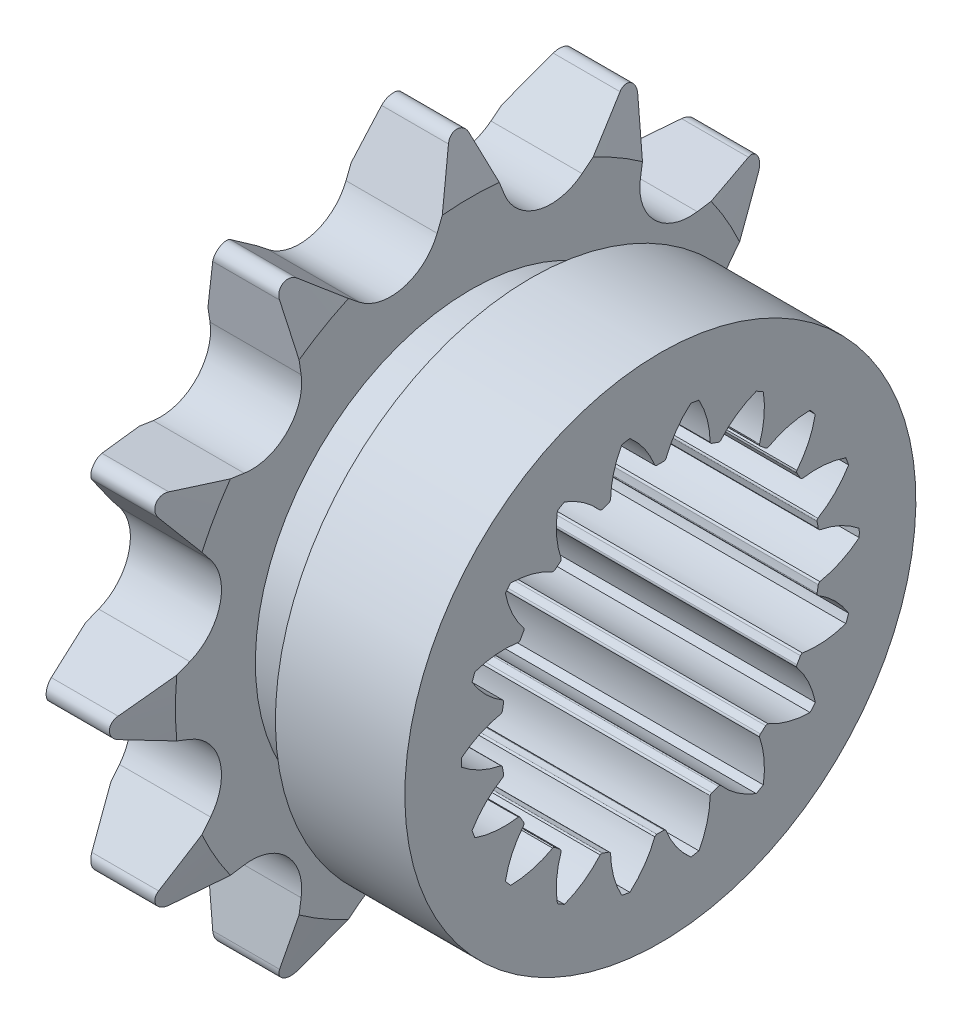
SolidWorks part; units mm, degrees
material "1144"
ref_plane "Front Plane" through (0, 0, 0) normal (0, 0, 1) x (1, 0, 0)
ref_plane "Top Plane" through (0, 0, 0) normal (0, 1, 0) x (1, 0, 0)
ref_plane "Right Plane" through (0, 0, 0) normal (1, 0, 0) x (0, 0, -1)
ref_axis "Axis1" through (-63.0158, 0, 0) along (1, 0, 0)
sketch "Sketch1" plane through (0, 0, 0) normal (0, 0, 1) x (1, 0, 0)
  line L0 (3.6068, 17.0561) -> (3.6068, 0) construction
  line L1 (22.225, 0) -> (22.225, 20.2311)
  line L3 (7.2136, 17.0561) -> (0, 17.0561)
  line L7 (0, 27.5082) -> (0, 30.0482) construction
  line L8 (0, 27.5082) -> (7.2136, 27.5082)
  line L9 (22.225, 0) -> (0, 0)
  line L10 (0, 0) -> (-84.1773, 0) construction
  line L11 (0, 17.0561) -> (0, 27.5082) construction
  line L12 (7.2136, 27.5082) -> (73.2462, 27.5082) construction
  line L13 (22.225, 0) -> (22.225, -20.2311) construction
  line L14 (3.6068, 0) -> (3.6068, -17.0561)
  line L15 (-15.4432, -17.0561) -> (22.6568, -17.0561)
  point P11 (0, 30.0482)
  dimension "D1" = 2.54
  dimension "hub_dia" = 40.4622
  dimension "width_teetth" = 7.2136
  dimension "D2" = 38.1
  dimension "length_thru" = 22.225
  dimension "OD" = 55.0164
  dimension "length_over_teeth" = 7.2136
  dimension "recess_hub_diam" = 34.1122
  dimension "hub_type" = 22.225
  dimension "projection 1" = 15.0114
  dimension "projection 2" = 0
sketch "Sketch2" plane through (0, 0, 0) normal (1, 0, 0) x (0, 0, -1)
  line L0 (0, 0) -> (0, 27.5082) construction
  line L1 (0, 0) -> (-13.7541, 23.8228) construction
  line L2 (0, 0) -> (-6.3502, 23.6991) construction
  line L3 (-0.8057, 26.9597) -> (-2.6638, 22.246)
  line L4 (-2.6638, 22.246) -> (-6.3502, 23.6991) construction
  line L5 (-0.8217, 27.4959) -> (0, 0) construction
  line L6 (-2.735, 27.3719) -> (0, 0) construction
  line L7 (-6.3502, 23.6991) -> (-2.4074, 24.0931) construction
  arc A1 (0, 27.5082) -> (-13.7541, 23.8228) centre (0, 0) ccw
  circle A2 centre (0, 0) radius 24.5351 construction
  circle A3 centre (-6.3502, 23.6991) radius 3.9624
  arc A4 (0, 27.5082) -> (-0.8057, 26.9597) centre (0, 26.6421) ccw
  dimension "pitch_diam" = 49.0703
  dimension "roller_diam" = 7.9248
  dimension "D1" = 1.712
  dimension "ang_1" = 30
  dimension "OD/2" = 27.5082
sketch "Taper Per Foot" plane through (0, 0, 0) normal (0, 0, 1) x (1, 0, 0)
  line L0 (22.225, 0) -> (22.225, 127)
  line L1 (22.225, 0) -> (22.225, 20.2311) construction
  line L2 (22.225, 127) -> (-282.575, 6.35)
  line L3 (-282.575, 6.35) -> (-282.575, 0)
  line L4 (-282.575, 0) -> (22.225, 0)
  line L5 (-282.575, 0) -> (-285.7823, 0) construction
  line L6 (-282.575, 6.35) -> (22.225, 6.35)
  line L7 (22.225, 6.35) -> (22.225, 127)
  dimension "1 Ft" = 304.8
  dimension "1 in" = 254
  dimension "Small End Diam" = 12.7
  dimension "Large End Diam" = 12.7
ref_plane "Plane1" through (7.2136, 0, 0) normal (1, 0, 0) x (0, 0, -1)
ref_plane "Plane2" through (7.2136, 0, 0) normal (1, 0, 0) x (0, 0, -1)
ref_plane "Plane3" through (0, 17.0561, 0) normal (-1, 0, 0) x (0, 0, 1)
ref_plane "Plane4" through (22.225, 0, 0) normal (1, 0, 0) x (0, 0, -1)
ref_plane "Plane5" through (3.6068, 0, 0) normal (1, 0, 0) x (0, 0, -1)
sketch "Sketch13" plane through (0, 0, 0) normal (0, 0, 1) x (1, 0, 0)
  line L0 (22.225, 0) -> (22.225, 20.2311) construction
  line L1 (0, 0) -> (22.225, 0)
  line L2 (0, 0) -> (0, 27.5082)
  line L3 (0, 27.5082) -> (22.225, 27.5082)
  line L4 (22.225, 0) -> (22.225, 27.5082)
revolve "Revolve1" add sketch "Sketch13" angle 360 about L10
sketch "Sketch6" plane through (0, -16.51, 0) normal (1, 0, 0) x (0, 0, -1)
  line L0 (-0.8057, 43.4697) -> (-2.6638, 38.756) construction
  line L1 (-0.8057, 43.4697) -> (-2.6638, 38.756)
  line L2 (-6.3502, 40.2091) -> (0, 16.51) construction
  line L3 (-12.7821, 40.2607) -> (-8.8161, 37.1075)
  arc A0 (0, 44.0182) -> (-0.8057, 43.4697) centre (0, 43.1521) ccw construction
  arc A1 (0, 44.0182) -> (-0.8057, 43.4697) centre (0, 43.1521) ccw
  arc A2 (-13.7541, 40.3328) -> (-12.7821, 40.2607) centre (-13.3211, 39.5828) cw
  arc A3 (-2.6638, 38.756) -> (-8.8161, 37.1075) centre (-6.3502, 40.2091) cw
  arc A4 (0, 44.0182) -> (-13.7541, 40.3328) centre (0, 16.51) ccw
extrude "Cut-Extrude1" cut sketch "Sketch6" along normal up to vertex (7.2136 mm away) up to point (7.2136, 17.0561, 0)
pattern_circular "CirPattern1" count 12 over 360 about axis through (-63.0158, 0, 0) along (1, 0, 0) of "Cut-Extrude1"
sketch "Sketch15" plane through (0, 0, 0) normal (0, 0, 1) x (1, 0, 0)
  line L1 (134.2136, 20.2311) -> (7.2136, 20.2311)
  line L2 (134.2136, 20.2311) -> (134.2136, 42.7482)
  line L3 (134.2136, 42.7482) -> (7.2136, 42.7482)
  line L4 (7.2136, 20.2311) -> (7.2136, 42.7482)
  line L5 (3.6068, 216.4797) -> (3.6068, 17.0561) construction
  line L6 (-127, 20.2311) -> (0, 20.2311)
  line L7 (0, 20.2311) -> (0, 42.7482)
  line L8 (-127, 42.7482) -> (0, 42.7482)
  line L9 (-127, 20.2311) -> (-127, 42.7482)
  dimension "D1" = 12.7
  dimension "D2" = 127
revolve "hub Cut-Revolve3" cut sketch "Sketch15" angle 360 about L10
sketch "Sketch4" plane through (0, 0, 0) normal (0, 0, 1) x (1, 0, 0)
  line L0 (0, 27.5082) -> (1.1045, 27.5082)
  line L2 (1.1045, 27.5082) -> (0, 23.3861)
  line L4 (0, 23.3861) -> (0, 27.5082)
  line L5 (3.6068, 27.5082) -> (3.6068, 44.9612) construction
  line L6 (7.2136, 27.5082) -> (6.1091, 27.5082)
  line L7 (7.2136, 23.3861) -> (7.2136, 27.5082)
  line L8 (6.1091, 27.5082) -> (7.2136, 23.3861)
  line L9 (0, 0) -> (-52.1231, 0) construction
  line L10 (0, 0) -> (-84.1773, 0) construction
  line L17 (0, 27.5082) -> (7.2136, 27.5082) construction
  dimension "D1" = 15
  dimension "D2" = 4.1221
revolve "Teeth Chamfer" cut sketch "Sketch4" angle 360 about L9
sketch "Sketch16" plane through (0, 0, 0) normal (0, 0, 1) x (1, 0, 0)
  line L1 (7.2136, 20.2311) -> (11.9761, 20.2311)
  line L2 (7.2136, 20.2311) -> (7.2136, 17.0561)
  line L3 (7.2136, 17.0561) -> (11.9761, 17.0561)
  line L4 (11.9761, 20.2311) -> (11.9761, 17.0561)
  line L5 (11.9761, 20.2311) -> (22.225, 20.2311) construction
  dimension "recess_width" = 4.7625
  dimension "recess_height" = 3.175
revolve "Recess" cut sketch "Sketch16" angle 360 about L10
sketch "Sketch32" plane through (22.225, 0, 0) normal (1, 0, 0) x (0, 0, -1)
  circle A1 centre (0, 0) radius 20.2311
  circle A2 centre (0, 0) radius 20.2311
  dimension "D1" = 0
extrude "Collar Reduction" [suppressed] cut sketch "Sketch32" against normal offset from surface (2.455 mm away) 19.77
ref_plane "Sprocket Teeth Center" through (3.6068, 0, 0) normal (-1, 0, 0) x (0, 0, 1)
sketch "Sketch35" plane through (3.6068, 0, 0) normal (1, 0, 0) x (0, 0, -1)
  circle A0 centre (0, 0) radius 24.5351 construction
  circle A1 centre (0, 0) radius 24.5351 construction
sketch "Sketch36" plane through (0, 0, 0) normal (-1, 0, 0) x (0, 0, 1)
  arc A34 (-7.5926, 13.7968) -> (-4.773, 11.8201) centre (-10.1337, 7.1728) cw
  arc A35 (-4.773, 11.8201) -> (-4.5847, 11.7902) centre (-4.6432, 12.0297) ccw
  arc A36 (-0.6644, 3.068) -> (-0.7894, 2.924) centre (-0.8986, 3.1451) cw
  arc A37 (-4.5847, 11.7902) -> (-4.0582, 11.9816) centre (0, 0) cw
  arc A38 (-8.1521, 13.4738) -> (-7.5639, 13.8125) centre (0, 0) cw
  arc A39 (-8.3407, 9.5111) -> (-7.9114, 9.8711) centre (0, 0) cw
  arc A40 (-7.85, 10.0436) -> (-7.9183, 9.8655) centre (-8.0965, 10.0359) cw
  arc A41 (-8.1521, 13.4738) -> (-7.85, 10.0436) centre (-1.145, 12.3625) ccw
  arc A42 (-2.4159, 15.5616) -> (-0.4424, 12.7398) centre (-7.0693, 10.2062) cw
  arc A43 (-0.4424, 12.7398) -> (-0.2757, 12.6472) centre (-0.2487, 12.8923) ccw
  arc A44 (-0.2757, 12.6472) -> (0.2845, 12.647) centre (0, 0) cw
  arc A45 (-3.0522, 15.4494) -> (-2.3836, 15.5666) centre (0, 0) cw
  arc A46 (-4.5847, 11.7902) -> (-4.0582, 11.9816) centre (0, 0) cw
  arc A47 (-3.9415, 12.1228) -> (-4.0666, 11.9788) centre (-4.1757, 12.1999) cw
  arc A48 (-3.0522, 15.4494) -> (-3.9415, 12.1228) centre (3.1523, 12.0085) ccw
  arc A49 (3.0522, 15.4494) -> (3.9415, 12.1228) centre (-3.1523, 12.0085) cw
  arc A50 (3.9415, 12.1228) -> (4.0666, 11.9788) centre (4.1757, 12.1999) ccw
  arc A51 (4.0666, 11.9788) -> (4.5929, 11.787) centre (0, 0) cw
  arc A52 (2.4159, 15.5616) -> (3.0842, 15.443) centre (0, 0) cw
  arc A53 (-0.2757, 12.6472) -> (0.2845, 12.647) centre (0, 0) cw
  arc A54 (0.4424, 12.7398) -> (0.2757, 12.6472) centre (0.2487, 12.8923) cw
  arc A55 (2.4159, 15.5616) -> (0.4424, 12.7398) centre (7.0693, 10.2062) ccw
  arc A56 (8.1521, 13.4738) -> (7.85, 10.0436) centre (1.145, 12.3625) cw
  arc A57 (7.85, 10.0436) -> (7.9183, 9.8655) centre (8.0965, 10.0359) ccw
  arc A58 (7.9183, 9.8655) -> (8.3473, 9.5053) centre (0, 0) cw
  arc A59 (7.5926, 13.7968) -> (8.18, 13.4568) centre (0, 0) cw
  arc A60 (4.0666, 11.9788) -> (4.5929, 11.787) centre (0, 0) cw
  arc A61 (4.773, 11.8201) -> (4.5847, 11.7902) centre (4.6432, 12.0297) cw
  arc A62 (7.5926, 13.7968) -> (4.773, 11.8201) centre (10.1337, 7.1728) ccw
  arc A63 (12.2688, 9.873) -> (10.8117, 6.753) centre (5.3042, 11.2253) cw
  arc A64 (10.8117, 6.753) -> (10.815, 6.5624) centre (11.0407, 6.6616) ccw
  arc A65 (10.815, 6.5624) -> (11.0949, 6.0771) centre (0, 0) cw
  arc A66 (11.8535, 10.368) -> (12.2892, 9.8476) centre (0, 0) cw
  arc A67 (7.9183, 9.8655) -> (8.3473, 9.5053) centre (0, 0) cw
  arc A68 (8.5279, 9.4748) -> (8.3407, 9.5111) centre (8.4775, 9.7162) cw
  arc A69 (11.8535, 10.368) -> (8.5279, 9.4748) centre (11.9758, 3.2743) ccw
  arc A70 (14.9057, 5.0814) -> (12.4694, 2.6479) centre (8.8236, 8.7342) cw
  arc A71 (12.4694, 2.6479) -> (12.4072, 2.4677) centre (12.6532, 2.4837) ccw
  arc A72 (12.4072, 2.4677) -> (12.5043, 1.916) centre (0, 0) cw
  arc A73 (14.6847, 5.6886) -> (14.9162, 5.0505) centre (0, 0) cw
  arc A74 (10.815, 6.5624) -> (11.0949, 6.0771) centre (0, 0) cw
  arc A75 (11.2542, 5.9867) -> (11.0907, 6.0849) centre (11.2894, 6.2307) cw
  arc A76 (14.6847, 5.6886) -> (11.2542, 5.9867) centre (12.3735, -1.0191) ccw
  arc A77 (15.7447, -0.3231) -> (12.623, -1.7765) centre (11.2787, 5.1896) cw
  arc A78 (12.623, -1.7765) -> (12.503, -1.9247) centre (12.7396, -1.9938) ccw
  arc A79 (12.503, -1.9247) -> (12.4055, -2.4763) centre (0, 0) cw
  arc A80 (15.7447, 0.3231) -> (15.744, -0.3557) centre (0, 0) cw
  arc A81 (12.4072, 2.4677) -> (12.5043, 1.916) centre (0, 0) cw
  arc A82 (12.623, 1.7765) -> (12.503, 1.9247) centre (12.7396, 1.9938) cw
  arc A83 (15.7447, 0.3231) -> (12.623, 1.7765) centre (11.2787, -5.1896) ccw
  arc A84 (14.6847, -5.6886) -> (11.2542, -5.9867) centre (12.3735, 1.0191) cw
  arc A85 (11.2542, -5.9867) -> (11.0907, -6.0849) centre (11.2894, -6.2307) ccw
  arc A86 (11.0907, -6.0849) -> (10.8104, -6.5699) centre (0, 0) cw
  arc A87 (14.9057, -5.0814) -> (14.6728, -5.719) centre (0, 0) cw
  arc A88 (12.503, -1.9247) -> (12.4055, -2.4763) centre (0, 0) cw
  arc A89 (12.4694, -2.6479) -> (12.4072, -2.4677) centre (12.6532, -2.4837) cw
  arc A90 (14.9057, -5.0814) -> (12.4694, -2.6479) centre (8.8236, -8.7342) ccw
  arc A91 (11.8535, -10.368) -> (8.5279, -9.4748) centre (11.9758, -3.2743) cw
  arc A92 (8.5279, -9.4748) -> (8.3407, -9.5111) centre (8.4775, -9.7162) ccw
  arc A93 (8.3407, -9.5111) -> (7.9114, -9.8711) centre (0, 0) cw
  arc A94 (12.2688, -9.873) -> (11.832, -10.3925) centre (0, 0) cw
  arc A95 (11.0907, -6.0849) -> (10.8104, -6.5699) centre (0, 0) cw
  arc A96 (10.8117, -6.753) -> (10.815, -6.5624) centre (11.0407, -6.6616) cw
  arc A97 (12.2688, -9.873) -> (10.8117, -6.753) centre (5.3042, -11.2253) ccw
  arc A98 (7.5926, -13.7968) -> (4.773, -11.8201) centre (10.1337, -7.1728) cw
  arc A99 (4.773, -11.8201) -> (4.5847, -11.7902) centre (4.6432, -12.0297) ccw
  arc A100 (4.5847, -11.7902) -> (4.0582, -11.9816) centre (0, 0) cw
  arc A101 (8.1521, -13.4738) -> (7.5639, -13.8125) centre (0, 0) cw
  arc A102 (8.3407, -9.5111) -> (7.9114, -9.8711) centre (0, 0) cw
  arc A103 (7.85, -10.0436) -> (7.9183, -9.8655) centre (8.0965, -10.0359) cw
  arc A104 (8.1521, -13.4738) -> (7.85, -10.0436) centre (1.145, -12.3625) ccw
  arc A105 (2.4159, -15.5616) -> (0.4424, -12.7398) centre (7.0693, -10.2062) cw
  arc A106 (0.4424, -12.7398) -> (0.2757, -12.6472) centre (0.2487, -12.8923) ccw
  arc A107 (0.2757, -12.6472) -> (-0.2845, -12.647) centre (0, 0) cw
  arc A108 (3.0522, -15.4494) -> (2.3836, -15.5666) centre (0, 0) cw
  arc A109 (4.5847, -11.7902) -> (4.0582, -11.9816) centre (0, 0) cw
  arc A110 (3.9415, -12.1228) -> (4.0666, -11.9788) centre (4.1757, -12.1999) cw
  arc A111 (3.0522, -15.4494) -> (3.9415, -12.1228) centre (-3.1523, -12.0085) ccw
  arc A112 (-3.0522, -15.4494) -> (-3.9415, -12.1228) centre (3.1523, -12.0085) cw
  arc A113 (-3.9415, -12.1228) -> (-4.0666, -11.9788) centre (-4.1757, -12.1999) ccw
  arc A114 (-4.0666, -11.9788) -> (-4.5929, -11.787) centre (0, 0) cw
  arc A115 (-2.4159, -15.5616) -> (-3.0842, -15.443) centre (0, 0) cw
  arc A116 (0.2757, -12.6472) -> (-0.2845, -12.647) centre (0, 0) cw
  arc A117 (-0.4424, -12.7398) -> (-0.2757, -12.6472) centre (-0.2487, -12.8923) cw
  arc A118 (-2.4159, -15.5616) -> (-0.4424, -12.7398) centre (-7.0693, -10.2062) ccw
  arc A119 (-8.1521, -13.4738) -> (-7.85, -10.0436) centre (-1.145, -12.3625) cw
  arc A120 (-7.85, -10.0436) -> (-7.9183, -9.8655) centre (-8.0965, -10.0359) ccw
  arc A121 (-7.9183, -9.8655) -> (-8.3473, -9.5053) centre (0, 0) cw
  arc A122 (-7.5926, -13.7968) -> (-8.18, -13.4568) centre (0, 0) cw
  arc A123 (-4.0666, -11.9788) -> (-4.5929, -11.787) centre (0, 0) cw
  arc A124 (-4.773, -11.8201) -> (-4.5847, -11.7902) centre (-4.6432, -12.0297) cw
  arc A125 (-7.5926, -13.7968) -> (-4.773, -11.8201) centre (-10.1337, -7.1728) ccw
  arc A126 (-12.2688, -9.873) -> (-10.8117, -6.753) centre (-5.3042, -11.2253) cw
  arc A127 (-10.8117, -6.753) -> (-10.815, -6.5624) centre (-11.0407, -6.6616) ccw
  arc A128 (-10.815, -6.5624) -> (-11.0949, -6.0771) centre (0, 0) cw
  arc A129 (-11.8535, -10.368) -> (-12.2892, -9.8476) centre (0, 0) cw
  arc A130 (-7.9183, -9.8655) -> (-8.3473, -9.5053) centre (0, 0) cw
  arc A131 (-8.5279, -9.4748) -> (-8.3407, -9.5111) centre (-8.4775, -9.7162) cw
  arc A132 (-11.8535, -10.368) -> (-8.5279, -9.4748) centre (-11.9758, -3.2743) ccw
  arc A133 (-14.9057, -5.0814) -> (-12.4694, -2.6479) centre (-8.8236, -8.7342) cw
  arc A134 (-12.4694, -2.6479) -> (-12.4072, -2.4677) centre (-12.6532, -2.4837) ccw
  arc A135 (-12.4072, -2.4677) -> (-12.5043, -1.916) centre (0, 0) cw
  arc A136 (-14.6847, -5.6886) -> (-14.9162, -5.0505) centre (0, 0) cw
  arc A137 (-10.815, -6.5624) -> (-11.0949, -6.0771) centre (0, 0) cw
  arc A138 (-11.2542, -5.9867) -> (-11.0907, -6.0849) centre (-11.2894, -6.2307) cw
  arc A139 (-14.6847, -5.6886) -> (-11.2542, -5.9867) centre (-12.3735, 1.0191) ccw
  arc A140 (-15.7447, 0.3231) -> (-12.623, 1.7765) centre (-11.2787, -5.1896) cw
  arc A141 (-12.623, 1.7765) -> (-12.503, 1.9247) centre (-12.7396, 1.9938) ccw
  arc A142 (-12.503, 1.9247) -> (-12.4055, 2.4763) centre (0, 0) cw
  arc A143 (-15.7447, -0.3231) -> (-15.744, 0.3557) centre (0, 0) cw
  arc A144 (-12.4072, -2.4677) -> (-12.5043, -1.916) centre (0, 0) cw
  arc A145 (-12.623, -1.7765) -> (-12.503, -1.9247) centre (-12.7396, -1.9938) cw
  arc A146 (-15.7447, -0.3231) -> (-12.623, -1.7765) centre (-11.2787, 5.1896) ccw
  arc A147 (-14.6847, 5.6886) -> (-11.2542, 5.9867) centre (-12.3735, -1.0191) cw
  arc A148 (-11.2542, 5.9867) -> (-11.0907, 6.0849) centre (-11.2894, 6.2307) ccw
  arc A149 (-11.0907, 6.0849) -> (-10.8104, 6.5699) centre (0, 0) cw
  arc A150 (-14.9057, 5.0814) -> (-14.6728, 5.719) centre (0, 0) cw
  arc A151 (-12.503, 1.9247) -> (-12.4055, 2.4763) centre (0, 0) cw
  arc A152 (-12.4694, 2.6479) -> (-12.4072, 2.4677) centre (-12.6532, 2.4837) cw
  arc A153 (-14.9057, 5.0814) -> (-12.4694, 2.6479) centre (-8.8236, 8.7342) ccw
  arc A154 (-11.8535, 10.368) -> (-8.5279, 9.4748) centre (-11.9758, 3.2743) cw
  arc A155 (-8.5279, 9.4748) -> (-8.3407, 9.5111) centre (-8.4775, 9.7162) ccw
  arc A156 (-8.3407, 9.5111) -> (-7.9114, 9.8711) centre (0, 0) cw
  arc A157 (-12.2688, 9.873) -> (-11.832, 10.3925) centre (0, 0) cw
  arc A158 (-11.0907, 6.0849) -> (-10.8104, 6.5699) centre (0, 0) cw
  arc A159 (-10.8117, 6.753) -> (-10.815, 6.5624) centre (-11.0407, 6.6616) cw
  arc A160 (-12.2688, 9.873) -> (-10.8117, 6.753) centre (-5.3042, 11.2253) ccw
  point P6 (-8.1521, 13.4738)
  point P24 (-3.1758, 15.7377)
  point P38 (2.2923, 15.8499)
  point P52 (7.469, 14.0851)
  point P66 (11.7299, 10.6563)
  point P81 (14.5611, 5.9769)
  point P95 (15.6211, 0.6114)
  point P109 (14.7821, -4.7931)
  point P123 (12.1452, -9.5847)
  point P137 (8.0286, -13.1855)
  point P151 (2.9286, -15.1611)
  point P165 (-2.5394, -15.2733)
  point P179 (-7.7161, -13.5085)
  point P193 (-11.977, -10.0797)
  point P207 (-14.8082, -5.4003)
  point P221 (-15.8682, -0.0348)
  point P235 (-15.0292, 5.3697)
  point P248 (-12.3924, 10.1613)
  point P258 (-0.1236, 0.2883)
extrude "Cut-Extrude2" cut sketch "Sketch36" against normal through all contours A157 A160 A159 A149 A148 A147 A150 A153 A152 A142 A141 A140 A143 A146 A145 A135 A134 A133 A136 A139 A138 A128 A127 A126 A129 A132 A131 A121 A120 A119 A122 A125 A124 A114 A113 A112 region at (0, 0, 0)
ref_axis "Axis2" through (22.225, 0, 0) along (-1, 0, 0)
